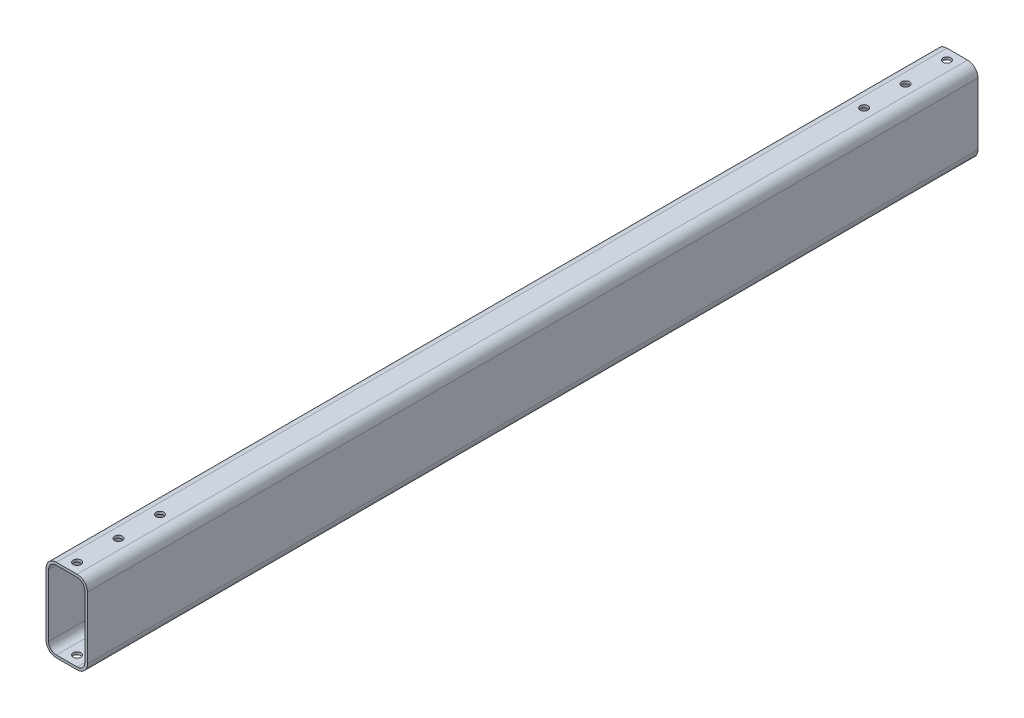
SolidWorks part; units mm, degrees
material "6061-T6 (SS)"
ref_plane "Front Plane" through (0, 0, 0) normal (0, 0, 1) x (1, 0, 0)
ref_plane "Top Plane" through (0, 0, 0) normal (0, 1, 0) x (1, 0, 0)
ref_plane "Right Plane" through (0, 0, 0) normal (1, 0, 0) x (0, 0, -1)
sketch "Sketch1" plane through (0, 0, 0) normal (0, 0, 1) x (1, 0, 0)
  line L1 (-6.35, -25.4) -> (6.35, -25.4)
  line L2 (-12.7, -19.05) -> (-12.7, 19.05)
  line L3 (-6.35, 25.4) -> (6.35, 25.4)
  line L4 (12.7, -19.05) -> (12.7, 19.05)
  line L5 (-12.7, -25.4) -> (12.7, 25.4) construction
  line L6 (-12.7, 25.4) -> (12.7, -25.4) construction
  arc A0 (-12.7, -19.05) -> (-6.35, -25.4) centre (-6.35, -19.05) ccw
  arc A1 (6.35, -25.4) -> (12.7, -19.05) centre (6.35, -19.05) ccw
  arc A2 (6.35, 25.4) -> (12.7, 19.05) centre (6.35, 19.05) cw
  arc A3 (-12.7, 19.05) -> (-6.35, 25.4) centre (-6.35, 19.05) cw
  point P0 (0, 0)
  dimension "D3" = 6.35
  dimension "D1" = 50.8
  dimension "D2" = 25.4
extrude "Extrude-Thin1" add sketch "Sketch1" along normal blind 546.1 thin thin type one direction reverse wall 1.5875
hole_wizard "3/16 (0.1875) Diameter Hole1" positions "3DSketch1" profile "Sketch3" hole size "3/16" standard "ANSI Inch" end condition through all
sketch3d "3DSketch1"
  line L1 (6.35, 25.4, 0) -> (-6.35, 25.4, 0) construction
  line L6 (0, 25.4, 546.1) -> (0, 25.4, 0) construction
  line L7 (6.35, 25.4, 546.1) -> (-6.35, 25.4, 546.1) construction
  point P57 (0, 25.4, 6.35)
  point P59 (0, 25.4, 31.75)
  point P61 (0, 25.4, 57.15)
  point P63 (0, 25.4, 514.35)
  point P65 (0, 25.4, 488.95)
  point P67 (0, 25.4, 539.75)
  dimension "D1" = 25.4
  dimension "D2" = 25.4
  dimension "D3" = 6.35
  dimension "D4" = 25.4
  dimension "D5" = 25.4
  dimension "D6" = 6.35
sketch "Sketch3" plane through (0, 25.4, 539.75) normal (1, 0, 0) x (0, 0, 1)
  line L0 (0, 0) -> (0, 50.8)
  line L1 (0, 50.8) -> (2.3812, 50.8)
  line L2 (2.3812, 50.8) -> (2.3812, 0)
  line L5 (2.3812, 0) -> (0, 0)
  line L11 (0, -6.35) -> (0, 107.95) construction
  dimension "Thru Hole Dia." = 4.7625
  dimension "Thru Hole Depth" = 50.8
